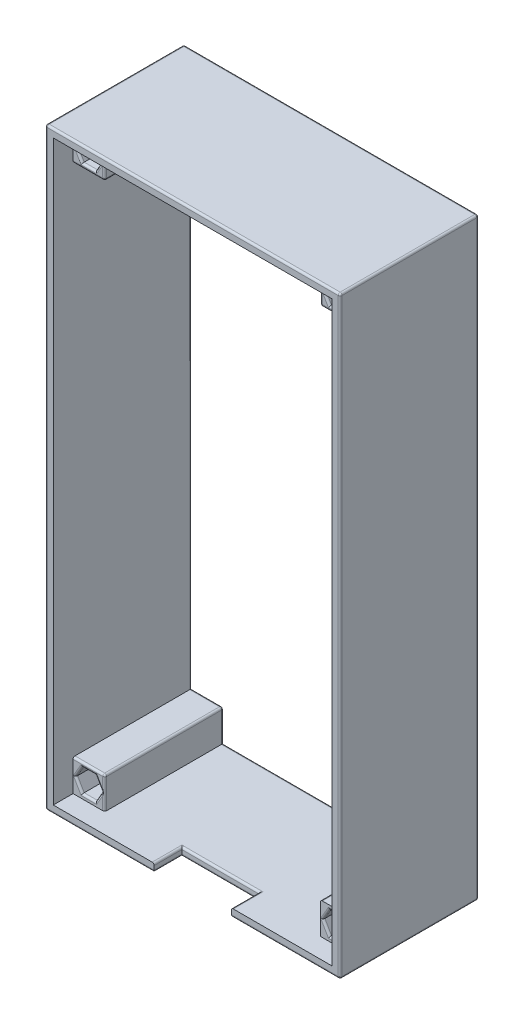
SolidWorks part; units mm, degrees
ref_plane "Front Plane" through (0, 0, 0) normal (0, 0, 1) x (1, 0, 0)
ref_plane "Top Plane" through (0, 0, 0) normal (0, 1, 0) x (1, 0, 0)
ref_plane "Right Plane" through (0, 0, 0) normal (1, 0, 0) x (0, 0, -1)
sketch "Sketch1" plane through (0, 0, 0) normal (0, 0, 1) x (1, 0, 0)
  line L0 (-35.25, -37.5) -> (-35.25, 35.5)
  line L1 (37.25, -37.5) -> (-37.25, -37.5)
  line L2 (37.25, -37.5) -> (37.25, 37.5)
  line L3 (37.25, 37.5) -> (-37.25, 37.5)
  line L4 (-37.25, -37.5) -> (-37.25, 37.5)
  line L5 (0, 37.5) -> (0, -37.5) construction
  line L6 (37.25, 0) -> (-37.25, 0) construction
  line L7 (35.25, 35.5) -> (-35.25, 35.5)
  line L8 (35.25, -37.5) -> (35.25, 35.5)
  line L9 (-31.25, 35.5) -> (-31.25, 31.5) construction
  line L10 (-31.25, 31.5) -> (-35.25, 31.5) construction
  line L11 (35.25, 31.5) -> (31.25, 31.5) construction
  line L12 (31.25, 31.5) -> (31.25, 35.5) construction
  line L13 (-31.25, 31.5) -> (-27.25, 31.5) construction
  line L14 (27.9014, 31.5) -> (29.5757, 28.6)
  line L15 (29.5757, 28.6) -> (32.9243, 28.6)
  line L16 (32.9243, 28.6) -> (34.5986, 31.5)
  line L17 (34.5986, 31.5) -> (32.9243, 34.4)
  line L18 (32.9243, 34.4) -> (29.5757, 34.4)
  line L19 (29.5757, 34.4) -> (27.9014, 31.5)
  line L20 (-27.9014, 31.5) -> (-29.5757, 34.4)
  line L21 (-29.5757, 34.4) -> (-32.9243, 34.4)
  line L22 (-32.9243, 34.4) -> (-34.5986, 31.5)
  line L23 (-34.5986, 31.5) -> (-32.9243, 28.6)
  line L24 (-32.9243, 28.6) -> (-29.5757, 28.6)
  line L25 (-29.5757, 28.6) -> (-27.9014, 31.5)
  line L26 (-31.25, 31.5) -> (-31.25, 27.5) construction
  line L27 (31.25, 31.5) -> (31.25, 27.5) construction
  line L28 (31.25, 31.5) -> (27.25, 31.5) construction
  line L29 (27.25, 31.5) -> (27.25, 35.5)
  line L30 (27.25, 31.5) -> (27.25, 27.5)
  line L31 (27.25, 27.5) -> (31.25, 27.5)
  line L32 (31.25, 27.5) -> (35.25, 27.5)
  line L33 (-31.25, 27.5) -> (-35.25, 27.5)
  line L34 (-31.25, 27.5) -> (-27.25, 27.5)
  line L35 (-27.25, 27.5) -> (-27.25, 31.5)
  line L36 (-27.25, 31.5) -> (-27.25, 35.5)
  circle A0 centre (31.25, 31.5) radius 1.75
  circle A1 centre (31.25, 31.5) radius 2.9 construction
  circle A2 centre (-31.25, 31.5) radius 1.75
  circle A3 centre (-31.25, 31.5) radius 2.9 construction
  point P0 (0, 0)
  dimension "D8" = 3.5
  dimension "D9" = 5.8
  dimension "D1" = 74.5
  dimension "D2" = 75
  dimension "D5" = 4
  dimension "D6" = 4
  dimension "D3" = 2
extrude "Boss-Extrude3" add sketch "Sketch1" along normal blind 35 contours L8 L1 L2 L3 L4 L0 L7 region at (-36.25, -36.4429, 0)
extrude "Boss-Extrude4" add sketch "Sketch1<3>" along normal blind 30 contours L35 L36 L7 L0 L33 L34 L25 L24 L23 L22 L21 L20 | L31 L32 L8 L7 L29 L30 L19 L18 L17 L16 L15 L14 region at (-35.1369, 31.5, 0) region at (33.25, 27.6131, 0)
sketch "Sketch1<3>" plane through (0, 0, 0) normal (0, 0, 1) x (1, 0, 0) same geometry as "Sketch1"
extrude "Boss-Extrude5" add sketch "Sketch1<4>" along normal blind 25 contours L18 L19 L14 L15 L16 L17 A0 | L24 L25 L20 L21 L22 L23 A2 region at (28.8153, 32.9057, 0) region at (-28.8153, 30.0943, 0)
sketch "Sketch1<4>" plane through (0, 0, 0) normal (0, 0, 1) x (1, 0, 0) same geometry as "Sketch1"
mirror "Mirror1" about plane through (0, -37.5, 35) normal (0, -1, 0) of bodies 105
sketch "Sketch8" plane through (0, -112.5, 0) normal (0, -1, 0) x (1, 0, 0)
  line L0 (0, 35) -> (-9.75, 35)
  line L1 (37.25, 35) -> (-37.25, 35) construction
  line L2 (-9.75, 35) -> (-9.75, 28)
  line L3 (-9.75, 28) -> (9.75, 28)
  line L4 (9.75, 28) -> (9.75, 35)
  line L5 (9.75, 35) -> (0, 35)
  dimension "D1" = 7
  dimension "D2" = 19.5
extrude "Cut-Extrude2" cut sketch "Sketch8" against normal blind 10
fillet "Fillet2" radius 0.5 69 edges at (33, 31.5, 0) (-29.5, 31.5, 0) (37.25, -37.5, 0) (-37.25, -37.5, 0) (-35.25, -37.5, 0) (-31.25, 27.5, 0) (-27.25, 31.5, 0) (0, 35.5, 0) (27.25, 31.5, 0) (31.25, 27.5, 0) (35.25, -37.5, 0) (37.25, 37.5, 17.5) (-37.25, 37.5, 17.5) (0, 37.5, 0) (33, -106.5, 0) (-29.5, -106.5, 0) (31.25, -102.5, 0) (27.25, -106.5, 0) (0, -110.5, 0) (-27.25, -106.5, 0) (-31.25, -102.5, 0) (0, -112.5, 0) (-27.25, -102.5, 15) (-27.25, 27.5, 15) (27.25, -102.5, 15) (27.25, 27.5, 15) (37.25, -112.5, 17.5) (37.25, -37.5, 35) (0, 37.5, 35) (-37.25, -37.5, 35) (23.5, -112.5, 35) (-37.25, -112.5, 17.5) (-23.5, -112.5, 35) (-9.75, -112.5, 31.5) (0, -112.5, 28) (9.75, -112.5, 31.5) (33.7615, -105.05, 30) (33.7615, -107.95, 30) (31.25, -109.4, 30) (28.7385, -107.95, 30) (28.7385, -105.05, 30) (31.25, -103.6, 30) (-28.7385, -105.05, 30) (-28.7385, -107.95, 30) (-31.25, -109.4, 30) (-33.7615, -107.95, 30) (-33.7615, -105.05, 30) (-31.25, -103.6, 30) (28.7385, 32.95, 30) (31.25, 34.4, 30) (28.7385, 30.05, 30) (31.25, 28.6, 30) (33.7615, 30.05, 30) (33.7615, 32.95, 30) (-33.7615, 30.05, 30) (-31.25, 28.6, 30) (-28.7385, 30.05, 30) (-28.7385, 32.95, 30) (-33.7615, 32.95, 30) (-31.25, 34.4, 30) (-31.25, -102.5, 30) (-27.25, -106.5, 30) (-31.25, 27.5, 30) (-27.25, 31.5, 30) (27.25, 31.5, 30) (31.25, 27.5, 30) (9.75, -110.5, 31.5) (-9.75, -110.5, 31.5) (0, -110.5, 28)
